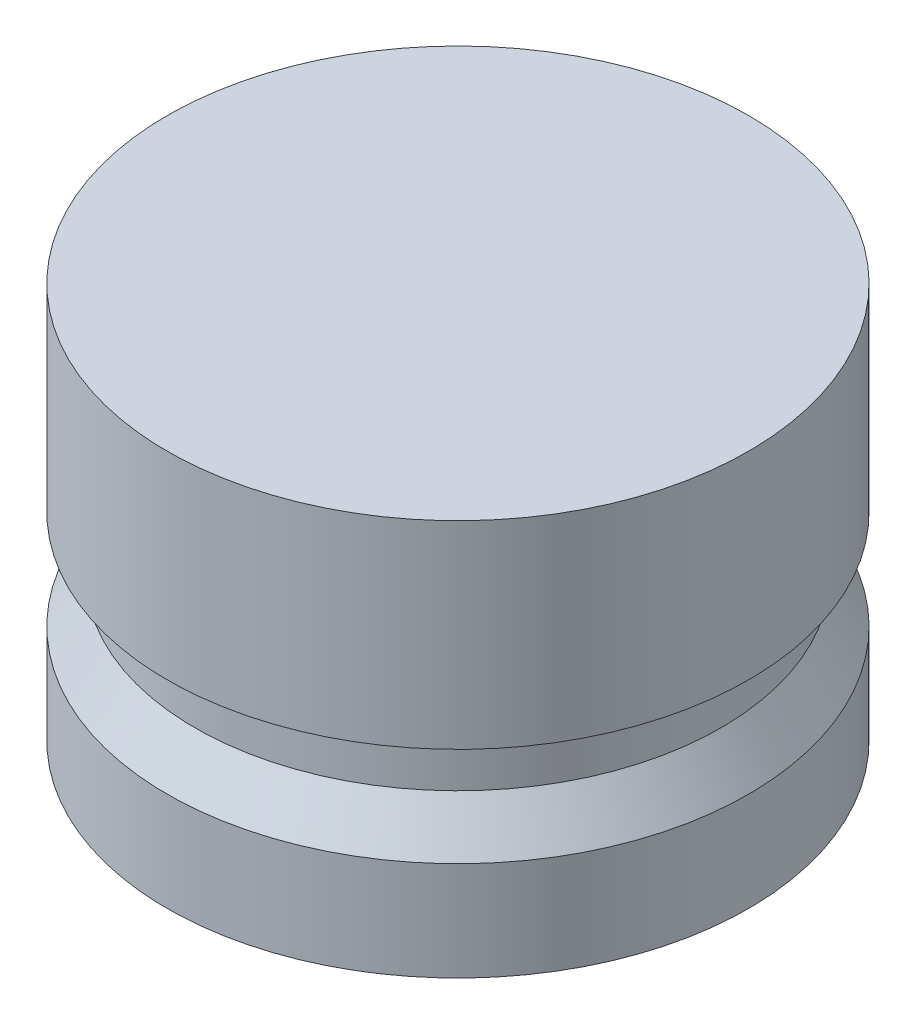
SolidWorks part; units mm, degrees
ref_plane "Front Plane" through (0, 0, 0) normal (0, 0, 1) x (1, 0, 0)
ref_plane "Top Plane" through (0, 0, 0) normal (0, 1, 0) x (1, 0, 0)
ref_plane "Right Plane" through (0, 0, 0) normal (1, 0, 0) x (0, 0, -1)
sketch "Sketch1" plane through (0, 0, 0) normal (0, 0, 1) x (1, 0, 0)
  line L0 (0, 0) -> (0, 12.7) construction
  line L1 (0, 0) -> (-9.3218, 0)
  line L2 (-9.3218, 0) -> (-9.3218, 3.175)
  line L4 (-8.4328, 4.572) -> (-8.4328, 6.35)
  line L5 (-8.4328, 6.35) -> (-9.3218, 6.35)
  line L6 (-9.3218, 6.35) -> (-9.3218, 12.7)
  line L7 (-9.3218, 12.7) -> (0, 12.7)
  line L8 (-9.525, 16.6801) -> (-9.525, -9.6051) construction
  line L9 (0, 0) -> (0, 12.7)
  line L10 (-8.4328, 4.572) -> (-9.3218, 3.175)
  dimension "D1" = 12.7
  dimension "D2" = 9.3218
  dimension "D3" = 1.778
  dimension "D4" = 3.175
  dimension "D5" = 9.525
  dimension "D6" = 8.4328
  dimension "D7" = 6.35
revolve "Revolve1" add sketch "Sketch1" angle 360 about L9
